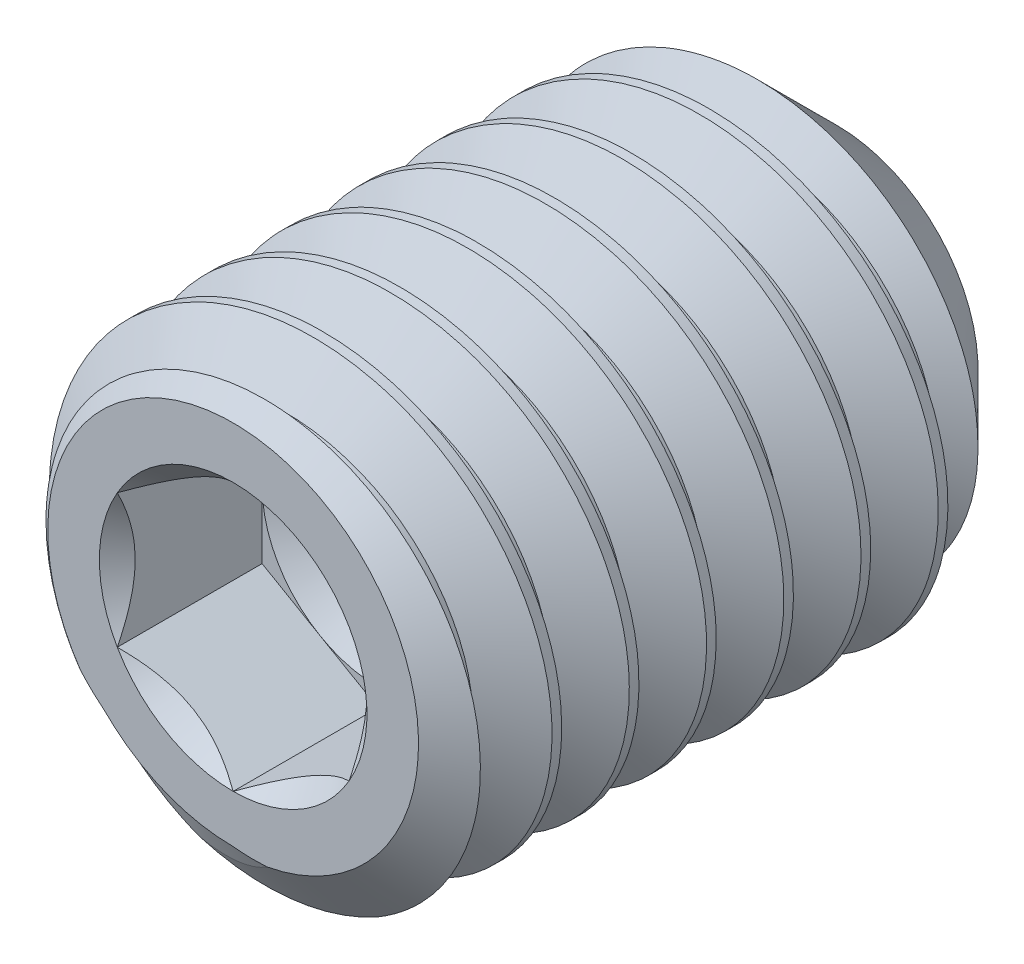
SolidWorks part; units mm, degrees
material "Nylon 6/10"
ref_plane "Front" through (0, 0, 0) normal (0, 0, 1) x (1, 0, 0)
ref_plane "Top" through (0, 0, 0) normal (0, 1, 0) x (1, 0, 0)
ref_plane "Right" through (0, 0, 0) normal (1, 0, 0) x (0, 0, -1)
sketch "Sketch22" plane through (0, 0, 0) normal (1, 0, 0) x (0, 0, -1)
  line L0 (-5.566, 0) -> (-5.566, 3.81)
  line L1 (-5.566, 3.81) -> (-4.899, 4.7625)
  line L2 (-4.899, 4.7625) -> (4.9812, 4.7625)
  line L3 (4.9812, 4.7625) -> (7.134, 2.6097)
  line L4 (7.134, 2.6097) -> (5.566, 0) construction
  line L5 (5.566, 0) -> (-5.566, 0)
  line L6 (5.566, 0) -> (7.134, 0) construction
  line L7 (7.134, 0) -> (7.134, 2.6097) construction
  line L8 (7.134, -2.6097) -> (5.566, 0) construction
  line L9 (-4.899, -4.7625) -> (4.9812, -4.7625) construction
  line L10 (7.134, 2.6097) -> (7.134, 0)
  line L11 (7.134, 0) -> (5.566, 0)
  dimension "Dia" = 9.525
  dimension "Length" = 12.7
  dimension "D3" = 35
  dimension "D5" = 118
  dimension "D6" = 45
  dimension "D7" = 7.62
revolve "Revolve1" add sketch "Sketch22" angle 360 about L6
ref_plane "Plane1" through (0, 0, -7.134) normal (0, 0, 1) x (1, 0, 0)
sketch "Sketch27" plane through (0, 0, -7.134) normal (0, 0, 1) x (1, 0, 0)
  circle A0 centre (0, 0) radius 4.7625 construction
  circle A1 centre (0, 0) radius 4.7625
curve "Helix/Spiral1" pitch 1.5875 height 14.2875 radius 4.7625 centre (0, 0, -7.134) axis (0, 0, 1) start towards (0, 1, 0)
sketch "Sketch28" plane through (0, 0, 0) normal (1, 0, 0) x (0, 0, -1)
  line L0 (7.134, 4.7625) -> (8.5231, 4.7625)
  line L1 (8.5231, 4.7625) -> (7.9278, 3.7314)
  line L2 (7.9278, 3.7314) -> (7.7293, 3.7314)
  line L3 (7.7293, 3.7314) -> (7.134, 4.7625)
  line L4 (7.4317, 4.2469) -> (8.2254, 4.2469) construction
  line L6 (-4.899, 4.7625) -> (4.9812, 4.7625) construction
  line L7 (7.134, 4.3586) -> (7.134, -4.3586) construction
  dimension "D1" = 0.1984
  dimension "D3" = 60
  dimension "D2" = 0.7937
sweep "Cut-Sweep2" cut profiles "Sketch28" path "Helix/Spiral1" align with end faces yes
sketch "Sketch23" plane through (0, 0, 5.566) normal (0, 0, 1) x (1, 0, 0)
  line L1 (0, 2.7496) -> (-2.3813, 1.3748)
  line L2 (-2.3813, 1.3748) -> (-2.3813, -1.3748)
  line L3 (-2.3813, -1.3748) -> (0, -2.7496)
  line L4 (0, -2.7496) -> (2.3812, -1.3748)
  line L5 (2.3812, -1.3748) -> (2.3812, 1.3748)
  line L6 (2.3812, 1.3748) -> (0, 2.7496)
  circle A0 centre (0, 0) radius 2.3813 construction
  dimension "Hex" = 4.7625
extrude "Cut-Extrude10" cut sketch "Sketch23" against normal blind 2.9766
sketch "Sketch24" plane through (0, 0, 5.566) normal (0, 0, 1) x (1, 0, 0)
  circle A0 centre (0, 0) radius 2.7496
extrude "Cut-Extrude11" cut sketch "Sketch24" against normal through all draft 45
sketch "Sketch26" plane through (0, 0, 2.5894) normal (0, 0, 1) x (1, 0, 0)
  circle A0 centre (0, 0) radius 2.3813 construction
  circle A1 centre (0, 0) radius 2.3813
extrude "Cut-Extrude12" cut sketch "Sketch26" against normal through all draft 60
sketch "Sketch30" plane through (0, 0, 0) normal (1, 0, 0) x (0, 0, -1)
  line L0 (-4.899, 4.7625) -> (4.9812, 4.7625) construction
  line L1 (-5.566, 0) -> (-5.566, 3.81) construction
  line L2 (7.134, 0) -> (7.134, 2.6097) construction
  line L3 (-4.899, -4.7625) -> (4.9812, -4.7625) construction
  point P0 (-5.566, 4.7625)
  point P1 (7.134, 4.7625)
  point P2 (7.134, -4.7625)
  point P11 (1.5778, -4.7625)
  dimension "D1" = 5.5562
sketch "Sketch31" plane through (0, 0, 0) normal (1, 0, 0) x (0, 0, -1)
  line L2 (5.566, 0) -> (7.134, -2.6097)
  line L3 (7.134, 2.6097) -> (5.566, 0)
hole_wizard "1/4 (0.25) Diameter Hole1" positions "Sketch32" profile "Sketch34" hole size "1/4" standard "ANSI Inch"
sketch "Sketch32" plane through (0, 0, -7.134) normal (0, 0, -1) x (-1, 0, 0)
  point P0 (0, 0)
sketch "Sketch34" plane through (0, 0, -7.134) normal (1, 0, 0) x (0, 1, 0)
  line L0 (0, 0) -> (0, 1.778)
  line L1 (0.7851, 1.5603) -> (3.175, 0.1243)
  line L2 (3.175, 0.1243) -> (3.175, 0)
  line L3 (0.7851, 1.5603) -> (0, 2.032) construction
  line L5 (3.175, 0) -> (0, 0)
  line L10 (0, 2.032) -> (-3.175, 0.1243) construction
  line L11 (0, -6.35) -> (0, 107.95) construction
  arc A0 (0, 1.778) -> (0.7851, 1.5603) centre (0, 0.2537) cw
  point P7 (0, 2.032)
  dimension "Hole Dia." = 6.35
  dimension "Hole Depth" = 2.032
  dimension "Drill Angle" = 118
sketch "Sketch35" plane through (0, 0, 2.5894) normal (0, 0, 1) x (1, 0, 0)
  line L0 (0, -1.5875) -> (0, 1.5875) construction
  circle A0 centre (0, 1.5875) radius 0.2553
  circle A1 centre (0, -1.5875) radius 0.2553
  point P4 (0, 0)
  dimension "D2" = 0.5105
  dimension "D1" = 3.175
extrude "Cut-Extrude13" cut sketch "Sketch35" against normal through all
equation "\"D7@Sketch22\"=\"Dia@Sketch22\"*.8"
equation "\"D1@Sketch28\" = \"D4@Helix/Spiral1\" * .125"
equation "\"D3@Helix/Spiral1\" = \"Length@Sketch22\" + \"D4@Helix/Spiral1\""
equation "\"D1@Sketch30\" = \"D4@Helix/Spiral1\" * 3.5"
equation "\"hex Depth@Cut-Extrude10\" = \"Hex@Sketch23\" * .625"
equation "\"D2@Sketch28\" = \"D4@Helix/Spiral1\" * .5"
